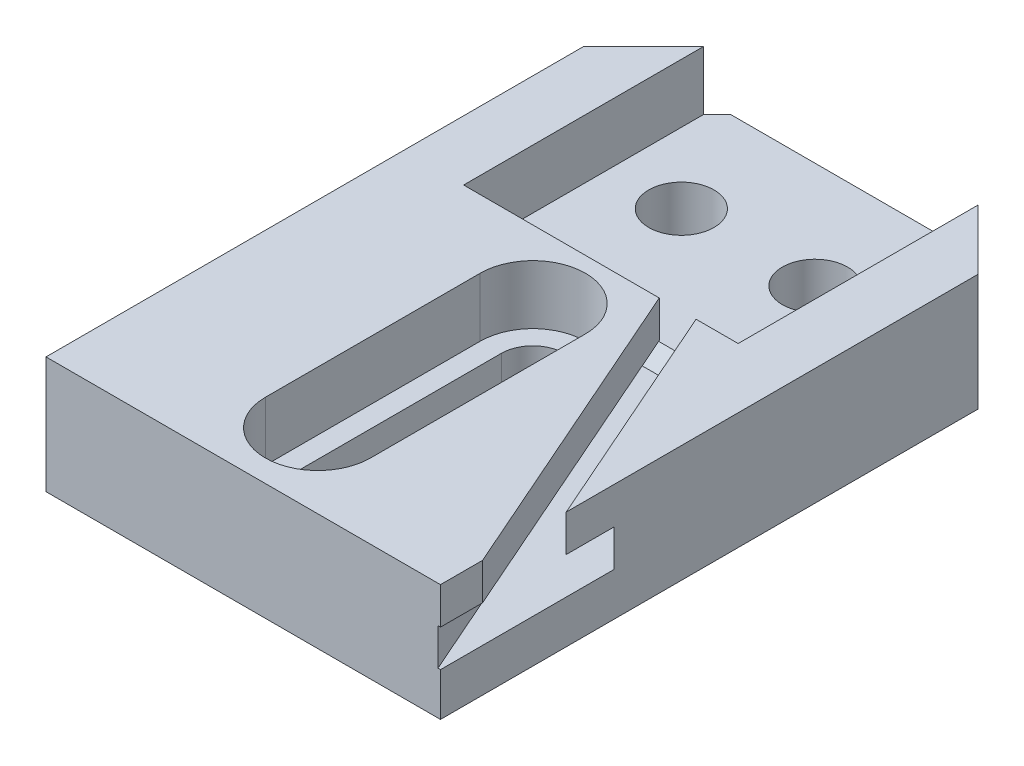
SolidWorks part; units mm, degrees
ref_plane "Front Plane" through (0, 0, 0) normal (0, 0, 1) x (1, 0, 0)
ref_plane "Top Plane" through (0, 0, 0) normal (0, 1, 0) x (1, 0, 0)
ref_plane "Right Plane" through (0, 0, 0) normal (1, 0, 0) x (0, 0, -1)
sketch "Sketch1" plane through (0, 0, 0) normal (0, 1, 0) x (1, 0, 0)
  line L1 (0, 0) -> (18.75, 0)
  line L2 (0, 0) -> (0, 29.05)
  line L3 (0, 29.05) -> (18.75, 29.05)
  line L4 (18.75, 0) -> (18.75, 29.05)
  dimension "D1" = 18.75
  dimension "D2" = 29.05
extrude "Boss-Extrude1" add sketch "Sketch1" along normal blind 5.55
sketch "MicroSwitchCutSketch2" plane through (0, 5.55, 0) normal (0, 1, 0) x (1, 0, 0)
  line L0 (18.75, 29.05) -> (0, 29.05) construction
  line L1 (2.85, 29.05) -> (15.9, 29.05)
  line L2 (2.85, 29.05) -> (2.85, 17)
  line L3 (2.85, 17) -> (15.9, 17)
  line L4 (15.9, 29.05) -> (15.9, 17)
  line L5 (0, 29.05) -> (0, 0) construction
  dimension "D1" = 13.05
  dimension "D2" = 2.85
  dimension "D3" = 12.05
extrude "MicroSwitchCut-Extrude1" cut sketch "MicroSwitchCutSketch2" against normal blind 2.8
sketch "MicroSwitchMountingHolesSketch3" plane through (0, 2.75, 0) normal (0, 1, 0) x (1, 0, 0)
  line L0 (2.85, 29.05) -> (2.85, 17) construction
  line L1 (15.9, 17) -> (15.9, 29.05) construction
  line L2 (2.85, 17) -> (15.9, 17) construction
  circle A0 centre (6.2, 24) radius 1.55
  circle A1 centre (12.55, 24) radius 1.55
  dimension "D4" = 3.1
  dimension "D1" = 3.35
  dimension "D2" = 3.35
  dimension "D3" = 7
extrude "MicroSwitchMountingHolesCut-Extrude2" cut sketch "MicroSwitchMountingHolesSketch3" against normal blind 3.1
sketch "GantryMountSlotSketch4" plane through (0, 5.55, 0) normal (0, 1, 0) x (1, 0, 0)
  line L0 (9.375, 13.7656) -> (9.375, 3.5507) construction
  line L1 (10.875, 13.7656) -> (10.875, 3.5507)
  line L2 (7.875, 13.7656) -> (7.875, 3.5507)
  line L3 (0, 29.05) -> (0, 0) construction
  arc A0 (10.875, 13.7656) -> (7.875, 13.7656) centre (9.375, 13.7656) ccw
  arc A1 (7.875, 3.5507) -> (10.875, 3.5507) centre (9.375, 3.5507) ccw
  point P2 (9.375, 8.6582)
  dimension "D2" = 9.375
extrude "SlidingMountHoleCut-Extrude3" cut sketch "GantryMountSlotSketch4" against normal through all
chamfer "Chamfer1" distance 3.5 angle 45 2 edges at (18.75, 2.775, -29.05) (0, 2.775, -29.05)
sketch "Sketch2" plane through (0, 5.55, 0) normal (0, 1, 0) x (1, 0, 0)
  line L0 (9.375, 3.5507) -> (9.375, 13.7656) construction
  line L1 (6.875, 3.5507) -> (6.875, 13.7656)
  line L2 (11.875, 3.5507) -> (11.875, 13.7656)
  line L5 (10.875, 3.5507) -> (10.875, 13.7656) construction
  arc A0 (6.875, 3.5507) -> (11.875, 3.5507) centre (9.375, 3.5507) ccw
  arc A1 (11.875, 13.7656) -> (6.875, 13.7656) centre (9.375, 13.7656) ccw
  arc A2 (10.875, 13.7656) -> (7.875, 13.7656) centre (9.375, 13.7656) ccw construction
  point P2 (9.375, 8.6582)
  point P15 (9.375, 15.2656)
  point P16 (9.375, 16.2656)
  dimension "D1" = 5
extrude "SlidingMountHoleBoreCut-Extrude4" cut sketch "Sketch2" against normal blind 2.8
sketch "Sketch3" plane through (0, 5.55, 0) normal (0, 1, 0) x (1, 0, 0)
  line L0 (12.15, 17) -> (18.75, 2)
  line L3 (18.75, 2) -> (18.75, 5.9773)
  line L4 (18.75, 5.9773) -> (13.9, 17)
  line L5 (13.9, 17) -> (12.15, 17)
  line L6 (2.85, 17) -> (15.9, 17) construction
  line L7 (18.75, 0) -> (18.75, 25.55) construction
  dimension "D1" = 1.75
  dimension "D2" = 2
  dimension "D3" = 2
extrude "ThinCableCut-Extrude5" cut sketch "Sketch3" against normal blind 1.75
sketch "Sketch4" plane through (0, 3.8, 0) normal (0, 1, 0) x (1, 0, 0)
  line L0 (11.15, 17) -> (18.75, -0.2727)
  line L1 (2.85, 17) -> (12.15, 17) construction
  line L2 (18.75, 0) -> (18.75, 2) construction
  line L3 (18.75, -0.2727) -> (18.75, 8.25)
  line L4 (18.75, 5.9773) -> (18.75, 25.55) construction
  line L5 (18.75, 8.25) -> (14.9, 17)
  line L6 (13.9, 17) -> (15.9, 17) construction
  line L7 (14.9, 17) -> (11.15, 17)
  line L10 (18.75, 5.9773) -> (13.9, 17) construction
  dimension "D1" = 3.75
extrude "ThickCableCut-Extrude6" cut sketch "Sketch4" against normal blind 1.75
chamfer "Chamfer2" distance 1 angle 45 1 edges at (13.025, 2.75, -17)
equation "\"GABWidthValue\"= 37.5mm"
equation "\"D1@Sketch1\" = \"XEndStopSupportWidth\""
equation "\"M2HeatInsertHoleDiameter\"= 3mm + .1mm'Add .1mm for printing"
equation "\"M2HeatInsertHoleDepth\"= 3.1mm'Spec"
equation "\"MicroSwitchMountingHoleOffsetFromBottom\"= 7mm"
equation "\"MicroSwitchTerminalHeight\"= 3.5mm"
equation "\"MicroSwitchDepth\"= 2.8mm"
equation "\"MicroSwitchCutOutLength\"= 13.05mm"
equation "\"MicroSwitchHeight\"= 6.55mm"
equation "\"MicroSwitchMountingHoleOffsetFromSide\"= 3.35mm"
equation "\"MicroSwitchExtraMountingHeight\"= 2mm"
equation "\"MicroSwitchCutOutHeight\"= \"MicroSwitchExtraMountingHeight\" + \"MicroSwitchTerminalHeight\" + \"MicroSwitchHeight\""
equation "\"EndStopCableDepth\"= 1.75mm"
equation "\"EndStopCableWidth\"= 3.75mm"
equation "\"GABLengthValue\"= 34mm"
equation "\"D2@Sketch1\"= \"XEndStopSupportLength\""
equation "\"D1@Boss-Extrude1\"=\"MicroSwitchHeight\" -1mm"
equation "\"D1@MicroSwitchCutSketch2\" = \"MicroSwitchCutOutLength\""
equation "\"D2@MicroSwitchCutSketch2\" = ( \"XEndStopSupportWidth\" - \"MicroSwitchCutOutLength\" ) / 2"
equation "\"D3@MicroSwitchCutSketch2\" = \"MicroSwitchCutOutHeight\""
equation "\"D1@MicroSwitchCut-Extrude1\"=\"MicroSwitchDepth\""
equation "\"D1@MicroSwitchMountingHolesSketch3\" = \"MicroSwitchMountingHoleOffsetFromSide\""
equation "\"D2@MicroSwitchMountingHolesSketch3\" = \"MicroSwitchMountingHoleOffsetFromSide\""
equation "\"D4@MicroSwitchMountingHolesSketch3\" = \"M2HeatInsertHoleDiameter\""
equation "\"D1@MicroSwitchMountingHolesCut-Extrude2\" = \"M2HeatInsertHoleDepth\""
equation "\"D3@MicroSwitchMountingHolesSketch3\"=\"MicroSwitchMountingHoleOffsetFromBottom\""
equation "\"XEndStopSupportWidth\"= \"GABWidthValue\" / 2"
equation "\"XEndStopSupportLength\"= \"GABLengthValue\" / 2 + \"MicroSwitchCutOutHeight\""
equation "\"M3HoleDiameter\"= 3mm"
equation "\"D1@GantryMountSlotSketch4\" = \"M3HoleDiameter\""
equation "\"D2@GantryMountSlotSketch4\" = \"XEndStopSupportWidth\" / 2"
equation "\"D1@Sketch2\"=\"M3HoleDiameter\" + 2mm"
equation "\"D2@Sketch2\"=1mm"
equation "\"D1@SlidingMountHoleBoreCut-Extrude4\"=\"MicroSwitchDepth\""
equation "\"D1@Sketch3\"=\"EndStopCableDepth\""
equation "\"D1@ThinCableCut-Extrude5\" = \"EndStopCableDepth\""
equation "\"D1@Sketch4\"=\"EndStopCableWidth\""
equation "\"D1@ThickCableCut-Extrude6\" = \"EndStopCableDepth\""
